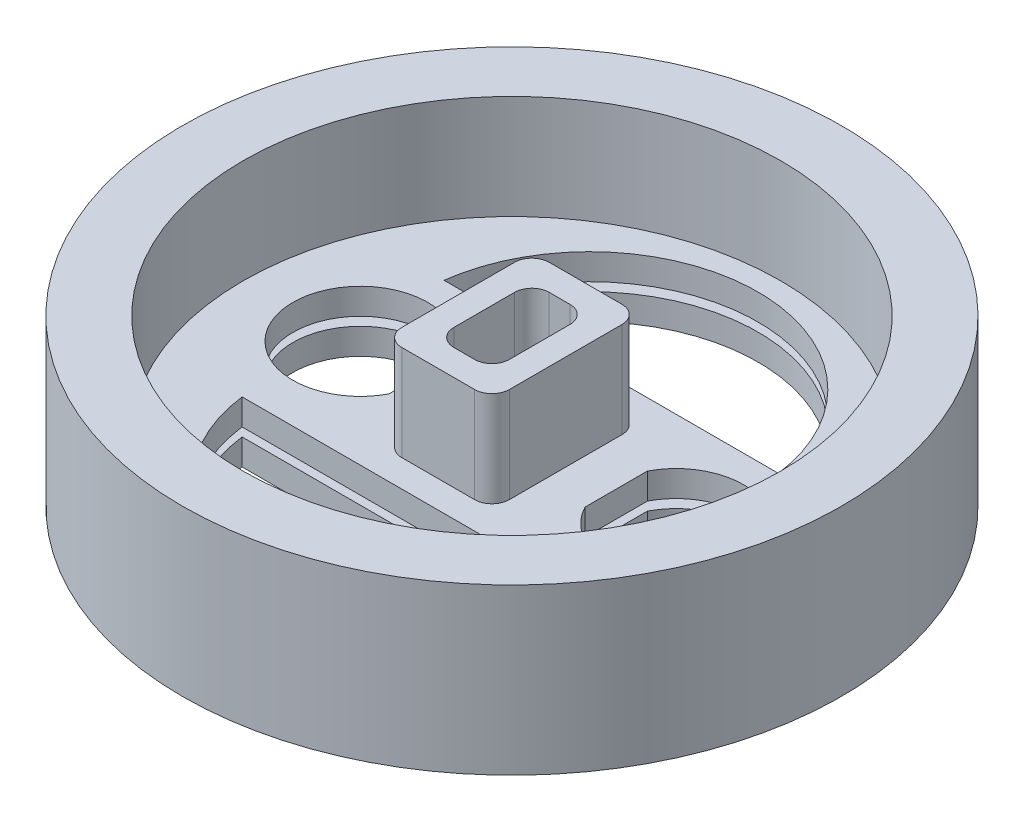
SolidWorks part; units mm, degrees
ref_plane "Front Plane" through (0, 0, 0) normal (0, 0, 1) x (1, 0, 0)
ref_plane "Top Plane" through (0, 0, 0) normal (0, 1, 0) x (1, 0, 0)
ref_plane "Right Plane" through (0, 0, 0) normal (1, 0, 0) x (0, 0, -1)
sketch "Sketch4" plane through (0, 0, 0) normal (0, 1, 0) x (1, 0, 0)
  line L0 (0, -46.7905) -> (24.3942, -46.7905) construction
  line L1 (0, -46.7905) -> (0, -24.9936) construction
  circle A0 centre (0, -46.7905) radius 17
  dimension "D1" = 34
extrude "Boss-Extrude3" add sketch "Sketch4" along normal blind 6 separate body
shell "Shell4" thickness 0.5 removed face at (0, 6, 63.7905) outward yes
ref_plane "Plane2" through (0, 0, 0) normal (0, 1, 0) x (1, 0, 0)
sketch "Sketch5" plane through (0, 0, 0) normal (0, 1, 0) x (1, 0, 0)
  line L0 (17, -46.7905) -> (-25.0436, -46.7905) construction
  line L1 (1.6, -44.0405) -> (-1.6, -44.0405)
  line L2 (1.6, -44.0405) -> (1.6, -49.5405)
  line L3 (1.6, -49.5405) -> (-1.6, -49.5405)
  line L4 (-1.6, -44.0405) -> (-1.6, -49.5405)
  line L5 (0, -29.7905) -> (0, -85.3723) construction
  circle A0 centre (0, -46.7905) radius 17 construction
  circle A1 centre (0, -46.7905) radius 17 construction
  dimension "D1" = 5.5
  dimension "D2" = 3.2
  dimension "D3" = 2.75
  dimension "D4" = 1.6
extrude "Boss-Extrude4" add sketch "Sketch5" along normal blind 7
shell "Shell5" thickness 1.5 removed face at (0, 7, 46.7905) outward yes
sketch "Sketch8" plane through (0, 1.5, 0) normal (0, 1, 0) x (1, 0, 0)
  line L0 (-9.7364, -40.9694) -> (9.5358, -40.9694)
  line L1 (3.1, -46.7905) -> (31.3222, -46.7905) construction
  line L2 (3.1, -51.0405) -> (3.1, -42.5405) construction
  line L3 (-9.7364, -52.6115) -> (9.5358, -52.6115)
  line L4 (-5.6513, -44.6283) -> (-5.6513, -48.2299)
  line L5 (0, -42.5405) -> (0, -27.4386) construction
  line L6 (3.1, -42.5405) -> (-3.1, -42.5405) construction
  line L7 (5.6513, -44.6283) -> (5.6513, -48.2299)
  arc A0 (-9.7364, -40.9694) -> (9.5358, -40.9694) centre (-0.1003, -42.217) cw
  arc A1 (-9.7364, -52.6115) -> (9.5358, -52.6115) centre (-0.1003, -51.3639) ccw
  arc A2 (-5.6513, -44.6283) -> (-5.6513, -48.2299) centre (-9.1002, -46.4291) ccw
  arc A3 (5.6513, -44.6283) -> (5.6513, -48.2299) centre (9.1002, -46.4291) cw
extrude "Cut-Extrude2" cut sketch "Sketch8" against normal through all
fillet "Fillet1" radius 1 8 edges at (-1.6, 3.5, 49.5405) (1.6, 3.5, 49.5405) (-1.6, 3.5, 44.0405) (1.6, 3.5, 44.0405) (-3.1, 4.25, 42.5405) (3.1, 4.25, 42.5405) (3.1, 4.25, 51.0405) (-3.1, 4.25, 51.0405)
